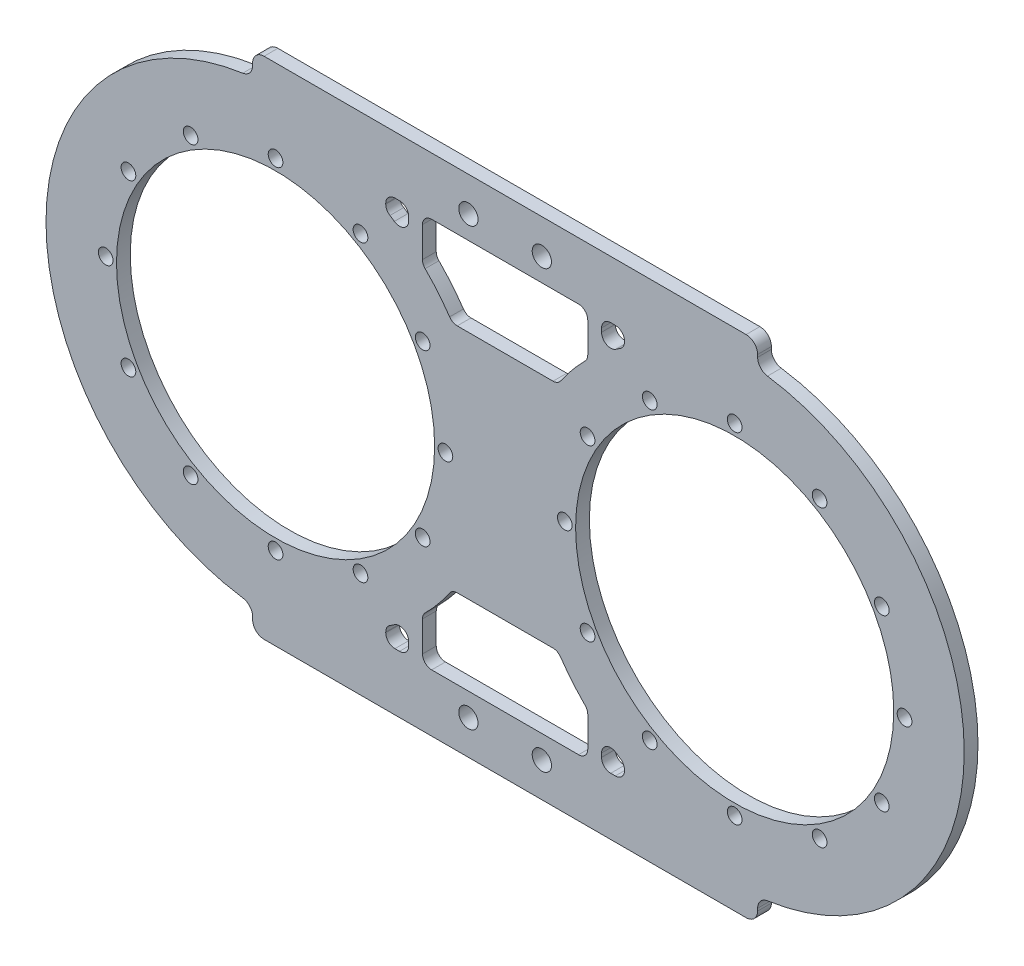
SolidWorks part; units mm, degrees
ref_plane "前视基准面" through (0, 0, 0) normal (0, 0, 1) x (1, 0, 0)
ref_plane "上视基准面" through (0, 0, 0) normal (0, 1, 0) x (1, 0, 0)
ref_plane "右视基准面" through (0, 0, 0) normal (1, 0, 0) x (0, 0, -1)
sketch "草图1" plane through (0, 0, 0) normal (0, 0, 1) x (1, 0, 0)
  line L7 (55, 55) -> (55, 49.7494)
  line L8 (-55, -55) -> (-55, -49.7494)
  line L10 (-55, 55) -> (55, 55)
  line L11 (55, -55) -> (55, -49.7494)
  line L12 (-55, -55) -> (55, -55)
  line L13 (-55, 55) -> (-55, 49.7494)
  line L14 (0, -55) -> (0, 55) construction
  line L15 (55, 0) -> (-55, 0) construction
  arc A0 (55, -49.7494) -> (55, 49.7494) centre (50, 0) ccw
  arc A1 (-55, -49.7494) -> (-55, 49.7494) centre (-50, 0) cw
  circle A2 centre (-50, 0) radius 34.65
  circle A3 centre (50, 0) radius 34.65
  circle A5 centre (-50, 37) radius 1.6
  circle A6 centre (-31.5, 32.0429) radius 1.6
  circle A7 centre (-17.9571, 18.5) radius 1.6
  circle A8 centre (-13, 0) radius 1.6
  circle A9 centre (-17.9571, -18.5) radius 1.6
  circle A10 centre (-31.5, -32.0429) radius 1.6
  circle A11 centre (-50, -37) radius 1.6
  circle A12 centre (-68.5, -32.0429) radius 1.6
  circle A13 centre (-82.0429, -18.5) radius 1.6
  circle A14 centre (-87, 0) radius 1.6
  circle A15 centre (-82.0429, 18.5) radius 1.6
  circle A16 centre (-68.5, 32.0429) radius 1.6
  circle A17 centre (68.5, 32.0429) radius 1.6
  circle A18 centre (50, 37) radius 1.6
  circle A19 centre (31.5, 32.0429) radius 1.6
  circle A20 centre (17.9571, 18.5) radius 1.6
  circle A21 centre (13, 0) radius 1.6
  circle A22 centre (17.9571, -18.5) radius 1.6
  circle A23 centre (31.5, -32.0429) radius 1.6
  circle A24 centre (50, -37) radius 1.6
  circle A25 centre (68.5, -32.0429) radius 1.6
  circle A26 centre (82.0429, -18.5) radius 1.6
  circle A27 centre (87, 0) radius 1.6
  circle A28 centre (82.0429, 18.5) radius 1.6
  circle A29 centre (-8, 47.5) radius 2.1
  circle A30 centre (8, 47.5) radius 2.1
  circle A31 centre (8, -47.5) radius 2.1
  circle A32 centre (-8, -47.5) radius 2.1
  point P41 (-50, 0)
  dimension "D1" = 12
extrude "凸台-拉伸1" add sketch "草图1" along normal blind 3
fillet "圆角1" radius 2.5 8 edges at (-55, 55, 1.5) (-55, 49.7494, 1.5) (-55, -55, 1.5) (-55, -49.7494, 1.5) (55, -49.7494, 1.5) (55, -55, 1.5) (55, 55, 1.5) (55, 49.7494, 1.5)
sketch "草图2" plane through (0, 0, 0) normal (0, 0, 1) x (1, 0, 0)
  line L4 (1.65, 0) -> (-1.65, 0) construction
  line L13 (18, 42.5) -> (18, 33.0454)
  line L17 (11.5007, 25.1755) -> (-11.5007, 25.1755)
  line L18 (-18, 42.5) -> (18, 42.5)
  line L19 (-21, 42.5) -> (-21, 35.7071)
  line L20 (-26, 42.5) -> (-21, 42.5)
  line L21 (-18, 42.5) -> (-18, 33.0454)
  line L22 (-26, 42.5) -> (-26, 39.2428)
  line L23 (-26, -42.5) -> (-26, -39.2428)
  line L24 (-18, -42.5) -> (-18, -33.0454)
  line L25 (-26, -42.5) -> (-21, -42.5)
  line L26 (-21, -42.5) -> (-21, -35.7071)
  line L27 (-18, -42.5) -> (18, -42.5)
  line L28 (11.5007, -25.1755) -> (-11.5007, -25.1755)
  line L31 (18, -42.5) -> (18, -33.0454)
  line L33 (0, -1.65) -> (0, 1.65) construction
  line L34 (21, -42.5) -> (21, -35.7071)
  line L35 (26, -42.5) -> (21, -42.5)
  line L36 (26, -42.5) -> (26, -39.2428)
  line L37 (26, 42.5) -> (26, 39.2428)
  line L38 (26, 42.5) -> (21, 42.5)
  line L39 (21, 42.5) -> (21, 35.7071)
  arc A1 (11.5007, 25.1755) -> (18, 33.0454) centre (50, 0) cw
  arc A5 (-21, 35.7071) -> (-26, 39.2428) centre (-50, 0) ccw
  arc A6 (-11.5007, 25.1755) -> (-18, 33.0454) centre (-50, 0) ccw
  arc A7 (-11.5007, -25.1755) -> (-18, -33.0454) centre (-50, 0) cw
  arc A8 (-21, -35.7071) -> (-26, -39.2428) centre (-50, 0) cw
  arc A10 (11.5007, -25.1755) -> (18, -33.0454) centre (50, 0) ccw
  arc A11 (21, -35.7071) -> (26, -39.2428) centre (50, 0) ccw
  arc A12 (21, 35.7071) -> (26, 39.2428) centre (50, 0) cw
  point P16 (0, 42.5)
  point P36 (0, -42.5)
extrude "切除-拉伸1" cut sketch "草图2" along normal blind 10
fillet "圆角2" radius 2 28 edges at (-18, -42.5, 1.5) (-11.5007, -25.1755, 1.5) (-18, -33.0454, 1.5) (-21, -42.5, 1.5) (-26, -42.5, 1.5) (-21, -35.7071, 1.5) (-26, -39.2428, 1.5) (18, 33.0454, 1.5) (11.5007, 25.1755, 1.5) (18, 42.5, 1.5) (-21, 35.7071, 1.5) (-18, 42.5, 1.5) (-21, 42.5, 1.5) (-26, 42.5, 1.5) (-26, 39.2428, 1.5) (-11.5007, 25.1755, 1.5) (-18, 33.0454, 1.5) (11.5007, -25.1755, 1.5) (18, -33.0454, 1.5) (18, -42.5, 1.5) (26, -42.5, 1.5) (26, -39.2428, 1.5) (21, -35.7071, 1.5) (21, -42.5, 1.5) (26, 42.5, 1.5) (26, 39.2428, 1.5) (21, 35.7071, 1.5) (21, 42.5, 1.5)
